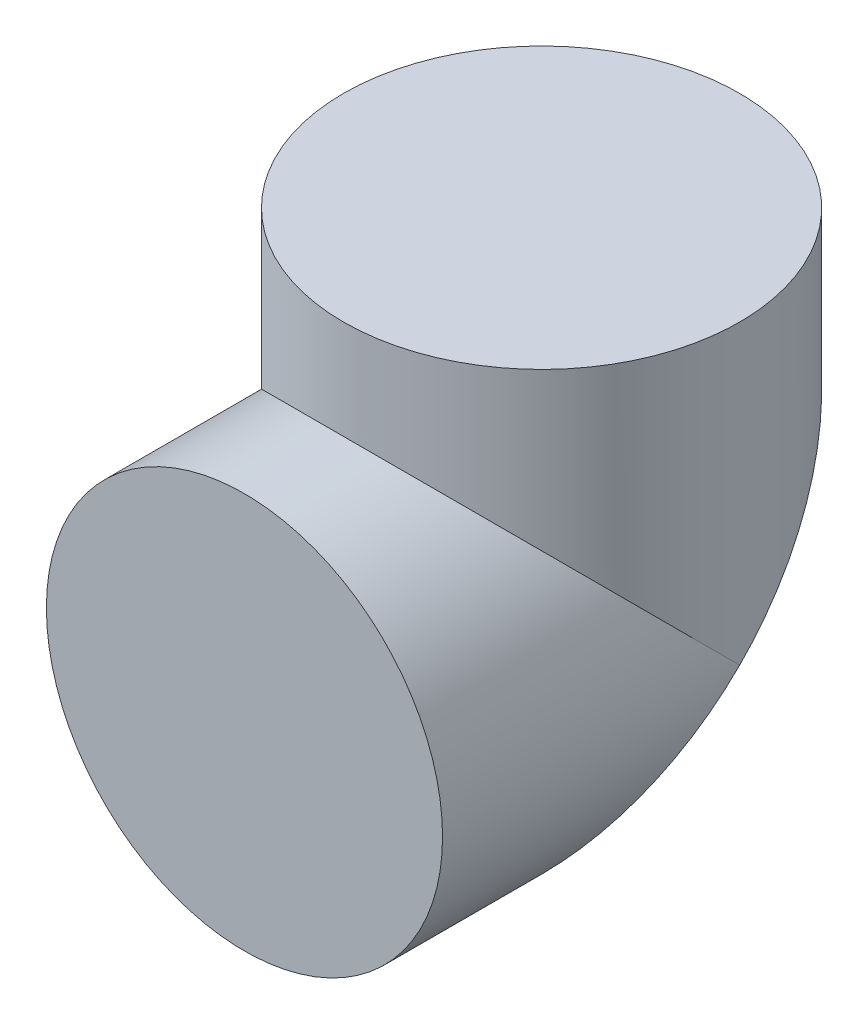
SolidWorks part; units mm, degrees
ref_plane "前视基准面" through (0, 0, 0) normal (0, 0, 1) x (1, 0, 0)
ref_plane "上视基准面" through (0, 0, 0) normal (0, 1, 0) x (1, 0, 0)
ref_plane "右视基准面" through (0, 0, 0) normal (1, 0, 0) x (0, 0, -1)
other "Configuration Table"
sketch "草图3" plane through (0, 0, 0) normal (0, 1, 0) x (1, 0, 0)
  circle A1 centre (0, -20) radius 20
extrude "凸台-拉伸2" add sketch "草图3" along normal blind 50
sketch "草图4" plane through (0, 0, 0) normal (0, 0, 1) x (1, 0, 0)
  circle A1 centre (0, 20) radius 20
extrude "凸台-拉伸3" add sketch "草图4" along normal blind 50
sketch "草图5" plane through (0, 0, 0) normal (1, 0, 0) x (0, 0, -1)
  line L0 (0, 40) -> (-40, 0)
  line L1 (-40, 0) -> (-40, -16.7973)
  line L2 (-40, -16.7973) -> (11.41, -16.7973)
  line L3 (11.41, -16.7973) -> (0, 40)
extrude "切除-拉伸1" cut sketch "草图5" against normal blind 40
sketch "草图6" plane through (0, 0, 0) normal (-1, 0, 0) x (0, 0, 1)
  line L0 (0, 40) -> (40, 0)
  line L1 (40, 0) -> (42.8401, -18.1759)
  line L2 (42.8401, -18.1759) -> (-20.8977, -9.0879)
  line L3 (-20.8977, -9.0879) -> (0, 40)
extrude "切除-拉伸2" cut sketch "草图6" against normal blind 40
ref_point "点2"
ref_point "点6"
sketch "草图7" plane through (0, 0, 50) normal (0, 0, 1) x (1, 0, 0)
  line L0 (0, 20) -> (0, 40)
  circle A0 centre (0, 20) radius 20 construction
sketch "草图8" plane through (0, 50, 0) normal (0, 1, 0) x (1, 0, 0)
  line L1 (0, -20) -> (-20, -20)
ref_axis "基准轴1" through (0, 20, 50) along (0, 0, 1)
ref_axis "基准轴2" through (0, 20, 50) along (0, 1, 0)
ref_axis "基准轴3" through (0, 50, 20) along (0, 1, 0)
ref_axis "基准轴4" through (0, 50, 20) along (-1, 0, 0)
